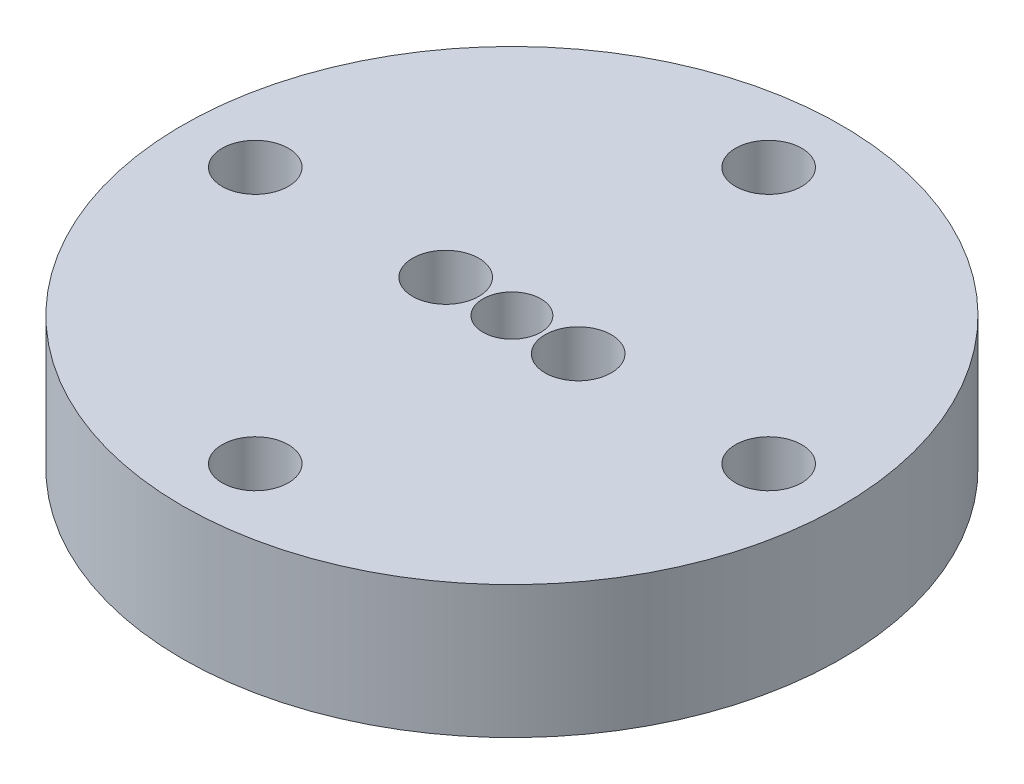
SolidWorks part; units mm, degrees
ref_plane "Front Plane" through (0, 0, 0) normal (0, 0, 1) x (1, 0, 0)
ref_plane "Top Plane" through (0, 0, 0) normal (0, 1, 0) x (1, 0, 0)
ref_plane "Right Plane" through (0, 0, 0) normal (1, 0, 0) x (0, 0, -1)
sketch "Sketch1" plane through (0, 0, 0) normal (0, 1, 0) x (1, 0, 0)
  circle A0 centre (0, 0) radius 15.5 construction
  circle A1 centre (0, 15.5) radius 2
  circle A2 centre (15.5, 0) radius 2
  circle A3 centre (0, -15.5) radius 2
  circle A4 centre (-15.5, 0) radius 2
  circle A5 centre (0, 0) radius 19.9
  circle A6 centre (0, 0) radius 4 construction
  circle A7 centre (-4, 0) radius 2
  circle A8 centre (4, 0) radius 2
  circle A9 centre (0, 0) radius 1.75
  point P14 (0, 0)
  dimension "D1" = 31
  dimension "D2" = 4
  dimension "D4" = 39.8
  dimension "D5" = 8
  dimension "D6" = 4
  dimension "D7" = 3.5
  dimension "D3" = 4
extrude "Boss-Extrude1" add sketch "Sketch1" along normal blind 8
